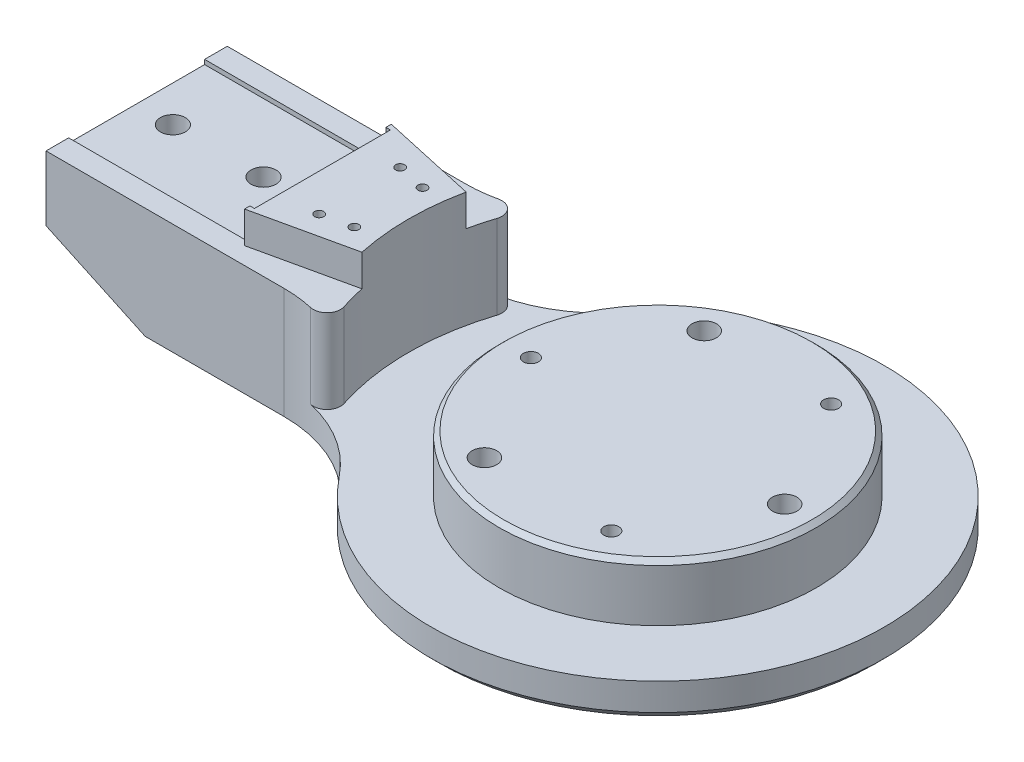
SolidWorks part; units mm, degrees
ref_plane "Front Plane" through (0, 0, 0) normal (0, 0, 1) x (1, 0, 0)
ref_plane "Top Plane" through (0, 0, 0) normal (0, 1, 0) x (1, 0, 0)
ref_plane "Right Plane" through (0, 0, 0) normal (1, 0, 0) x (0, 0, -1)
sketch "Sketch1" plane through (0, 0, 0) normal (0, 1, 0) x (1, 0, 0)
  circle A0 centre (0, 0) radius 35
  dimension "D1" = 70
extrude "Boss-Extrude1" add sketch "Sketch1" along normal blind 1
sketch "Sketch3" plane through (0, 0, 0) normal (0, -1, 0) x (1, 0, 0)
  line L1 (-28.2, -28.2) -> (28.2, -28.2) construction
  line L2 (-28.2, -28.2) -> (-28.2, 28.2) construction
  line L3 (-28.2, 28.2) -> (28.2, 28.2) construction
  line L4 (28.2, -28.2) -> (28.2, 28.2) construction
  line L5 (-28.2, -28.2) -> (28.2, 28.2) construction
  line L6 (-28.2, 28.2) -> (28.2, -28.2) construction
  circle A0 centre (0, 0) radius 50
  point P0 (0, 0)
  dimension "D2" = 100
  dimension "D1" = 56.4
extrude "Boss-Extrude3" add sketch "Sketch3" along normal blind 8
sketch "Sketch22" plane through (0, -8, 0) normal (0, -1, 0) x (1, 0, 0)
  line L0 (-50, 0) -> (-115, 0) construction
  line L1 (-45.8258, 20) -> (-115, 20)
  line L2 (-45.8258, -20) -> (-115, -20)
  line L4 (-115, 20) -> (-115, -20)
  line L5 (-1.6087, 20) -> (-95.5859, 20) construction
  line L6 (-1.6087, 0) -> (-95.5859, 0) construction
  line L7 (-1.6087, -20) -> (-95.5859, -20) construction
  circle A0 centre (0, 0) radius 50 construction
  arc A1 (-45.8258, 20) -> (-45.8258, -20) centre (0, 0) ccw
  dimension "D3" = 115
  dimension "D1" = 20
  dimension "D2" = 20
extrude "Boss-Extrude5" add sketch "Sketch22" against normal up to surface (8 mm away) up to face at (0, 0, 35)
sketch "Sketch24" plane through (0, 0, 0) normal (0, 1, 0) x (1, 0, 0)
  line L3 (-115, -20) -> (-51.2348, -20)
  line L4 (-115, 20) -> (-115, -20)
  line L5 (-51.2348, 20) -> (-115, 20)
  line L6 (0, 0) -> (-127.3918, 0) construction
  arc A0 (-51.2348, 20) -> (-51.2348, -20) centre (0, 0) ccw
  dimension "D1" = 110
  dimension "D2" = 40
  dimension "D3" = 115
extrude "Boss-Extrude6" add sketch "Sketch24" along normal blind 18.5
fillet "Fillet1" radius 30 2 edges at (-45.8258, -4, -20) (-45.8258, -4, 20)
sketch "Sketch25" plane through (-115, 0, 0) normal (-1, 0, 0) x (0, 0, 1)
  line L0 (-20, 18.5) -> (20, 18.5) construction
  line L1 (-15, 19.5) -> (15, 19.5)
  line L2 (-15, 19.5) -> (-15, 17.5)
  line L3 (-15, 17.5) -> (15, 17.5)
  line L4 (15, 19.5) -> (15, 17.5)
  line L5 (-15, 19.5) -> (15, 17.5) construction
  line L6 (-15, 17.5) -> (15, 19.5) construction
  point P0 (0, 18.5)
  dimension "D1" = 2
  dimension "D2" = 30
extrude "Cut-Extrude14" cut sketch "Sketch25" against normal blind 41
sketch "Sketch26" plane through (0, -8, 0) normal (0, -1, 0) x (1, 0, 0)
  line L0 (-110.0843, 0) -> (-45.9178, 0) construction
  line L3 (-115, 20) -> (-115, -20) construction
  circle A0 centre (-107, 0) radius 2.75
  circle A1 centre (-87, 0) radius 2.75
  dimension "D3" = 5.5
  dimension "D1" = 8
  dimension "D2" = 20
extrude "Cut-Extrude15" cut sketch "Sketch26" against normal through all
sketch "Sketch27" plane through (0, -8, 0) normal (0, -1, 0) x (1, 0, 0)
  line L1 (-82.2805, -0.3743) -> (-84.3161, 3.9)
  line L2 (-84.3161, 3.9) -> (-89.0356, 4.2743)
  line L3 (-89.0356, 4.2743) -> (-91.7195, 0.3743)
  line L4 (-91.7195, 0.3743) -> (-89.6839, -3.9)
  line L5 (-89.6839, -3.9) -> (-84.9644, -4.2743)
  line L6 (-84.9644, -4.2743) -> (-82.2805, -0.3743)
  line L7 (-102.2805, -0.3743) -> (-104.3161, 3.9)
  line L8 (-104.3161, 3.9) -> (-109.0356, 4.2743)
  line L9 (-109.0356, 4.2743) -> (-111.7195, 0.3743)
  line L10 (-111.7195, 0.3743) -> (-109.6839, -3.9)
  line L11 (-109.6839, -3.9) -> (-104.9644, -4.2743)
  line L12 (-104.9644, -4.2743) -> (-102.2805, -0.3743)
  circle A0 centre (-87, 0) radius 4.1 construction
  circle A1 centre (-107, 0) radius 4.1 construction
  dimension "D1" = 8.2
extrude "Cut-Extrude16" cut sketch "Sketch27" against normal blind 12
sketch "Sketch30" plane through (0, -8, 0) normal (0, -1, 0) x (1, 0, 0)
  line L0 (0, 0) -> (143.771, 0) construction
sketch "Sketch31" plane through (0, 18.5, 0) normal (0, 1, 0) x (1, 0, 0)
  line L0 (-55, 0) -> (-75, 0) construction
  line L2 (-53.7849, -11.4971) -> (-75, -16.2003)
  line L8 (-115, -15) -> (-115, -20)
  line L9 (-115, -20) -> (-62.45, -20)
  line L10 (-62.45, 20) -> (-115, 20)
  line L15 (-115, -15) -> (-115, -20)
  line L23 (-75, -16.2003) -> (-75, 16.2003)
  line L24 (-53.7849, 11.4971) -> (-75, 16.2003)
  line L25 (-74, -15) -> (-115, -15)
  line L26 (-115, 20) -> (-115, 15)
  line L27 (-115, 15) -> (-74, 15)
  line L28 (-74, 15) -> (-74, -15)
  arc A3 (-50.119, -22.6514) -> (-62.45, -20) centre (-62.45, -50) ccw
  arc A4 (-50.119, 22.6514) -> (-50.119, -22.6514) centre (0, 0) ccw
  arc A5 (-50.119, -22.6514) -> (-62.45, -20) centre (-62.45, -50) ccw
  arc A7 (-53.7849, 11.4971) -> (-53.7849, -11.4971) centre (0, 0) ccw
  arc A9 (-62.45, 20) -> (-50.119, 22.6514) centre (-62.45, 50) ccw
  arc A10 (-62.45, 20) -> (-50.119, 22.6514) centre (-62.45, 50) ccw
  point P13 (-52.3713, 0)
  point P25 (-69, 0)
  arc M18 (-50.119, -22.6514) -> (-50.119, 22.6514) centre (0, 0) cw
  dimension "D2" = 20
  dimension "D3" = 25
  dimension "D1" = 0
extrude "Boss-Extrude7" add sketch "Sketch31" along normal blind 13 contours L0 A7 L24 L23 | L0 L23 L2 M18 region at (-64.835, 18.5, 0)
sketch "Sketch33" plane through (0, 31.5, 0) normal (0, 1, 0) x (1, 0, 0)
  line L0 (-55.0152, -11.7698) -> (-67.9999, -14.6485)
  line L1 (-53.7849, -11.4971) -> (-75, -16.2003) construction
  line L2 (-53.7849, -11.4971) -> (-75, -16.2003) construction
  line L3 (-67.9999, -14.6485) -> (-70.1065, -5.1463)
  line L5 (-57.0191, -2.7309) -> (-55.0152, -11.7698)
  line L6 (-48.9387, 0) -> (-52.4764, 0) construction
  line L8 (-57.0191, 2.7309) -> (-55.0152, 11.7698)
  line L9 (-55.0152, 11.7698) -> (-67.9999, 14.6485)
  line L10 (-67.9999, 14.6485) -> (-70.1065, 5.1463)
  line L12 (-57.0191, -2.7309) -> (-57.0191, 2.7309)
  line L13 (-70.1065, -5.1463) -> (-75, -5.1463)
  line L14 (-75, -16.2003) -> (-75, -15) construction
  line L15 (-70.1065, 5.1463) -> (-75, 5.1463)
  line L16 (-75, -5.1463) -> (-75, 5.1463)
  line L17 (-53.7849, 11.4971) -> (-75, 16.2003) construction
  point P6 (-57.0191, 2.7309)
  dimension "D1" = 13.3
extrude "Cut-Extrude21" cut sketch "Sketch33" against normal blind 6 contours L10 L15 L16 L13 L3 L0 L5 L12 L8 L9
sketch "Sketch34" plane through (0, 25.5, 0) normal (0, 1, 0) x (1, 0, 0)
  line L0 (-61.5075, 13.2091) -> (-63.5857, 3.835) construction
  line L1 (-55.0152, 11.7698) -> (-67.9999, 14.6485) construction
  line L2 (-57.0191, 0) -> (-74, 0) construction
  line L3 (-57.0191, -2.7309) -> (-57.0191, 2.7309) construction
  line L4 (-74, 15) -> (-74, -15) construction
  line L5 (-69.4068, 8.3025) -> (-56.422, 5.4239) construction
  line L6 (-67.9999, 14.6485) -> (-70.1065, 5.1463) construction
  line L7 (-57.0191, 2.7309) -> (-55.0152, 11.7698) construction
  line L8 (-67.9999, 14.6485) -> (-70.1065, 5.1463) construction
  line L9 (-69.1038, 9.6693) -> (-56.119, 6.7907) construction
  line L10 (-66.0874, 7.5666) -> (-64.5658, 14.4302) construction
  circle A0 centre (-59.4384, -7.5266) radius 1
  circle A1 centre (-65.7843, -8.9335) radius 1
  circle A2 centre (-65.7843, 8.9335) radius 1
  circle A4 centre (-59.4384, 7.5266) radius 1
  point P30 (-59.5633, 7.5666)
  point P31 (0, 0)
  point P32 (-65.7426, 8.9242)
  point P33 (0, 0)
  point P34 (-59.5845, 7.559)
  point P35 (0, 0)
  point P36 (0, 0)
  dimension "D1" = 6.5
  dimension "D3" = 3.25
  dimension "D2" = 1.4
extrude "Cut-Extrude22" cut sketch "Sketch34" against normal blind 5
chamfer "Chamfer4" distance 1 angle 45 1 edges at (0, 1, 35)
fillet "Fillet3" radius 3 2 edges at (-50.119, 9.25, -22.6514) (-50.119, 9.25, 22.6514)
chamfer "Chamfer6" distance 10 angle 65 1 edges at (-115, -8, 0) first distance on face at (-115, 11.625, 0)
chamfer "Chamfer7" distance 2 angle 45 7 edges at (-104.2775, -3, 20) (-78.0025, -8, 20) (-49.4596, -8, 22.9584) (50, -8, 0) (-49.4596, -8, -22.9584) (-78.0025, -8, -20) (-104.2775, -3, -20)
sketch "Sketch37" plane through (0, 25.5, 0) normal (0, 1, 0) x (1, 0, 0)
  line L1 (-61.4174, -14.5064) -> (-48.5826, -14.5064)
  line L2 (-61.4174, -14.5064) -> (-61.4174, 14.5064)
  line L3 (-61.4174, 14.5064) -> (-48.5826, 14.5064)
  line L4 (-48.5826, -14.5064) -> (-48.5826, 14.5064)
  line L5 (-61.4174, -14.5064) -> (-48.5826, 14.5064) construction
  line L6 (-61.4174, 14.5064) -> (-48.5826, -14.5064) construction
  arc A0 (-52.3439, 16.8854) -> (-52.3439, -16.8854) centre (0, 0) ccw construction
  point P0 (-55, 0)
extrude "Cut-Extrude24" cut sketch "Sketch37" along normal blind 15
sketch "Sketch38" plane through (0, 25.5, 0) normal (0, 1, 0) x (1, 0, 0)
  circle A0 centre (-75.6748, -4.6987) radius 27.8917
extrude "Cut-Extrude25" cut sketch "Sketch38" along normal up to surface (6 mm away) up to face at (-72.6844, 31.5, 11.8569)
sketch "Sketch39" plane through (0, 0, 0) normal (0, 1, 0) x (1, 0, 0)
  circle A0 centre (0, 0) radius 35
extrude "Boss-Extrude8" add sketch "Sketch39" along normal blind 12.5
chamfer "Chamfer8" distance 1 angle 45 1 edges at (0, 12.5, 35)
sketch "Sketch40" plane through (0, 12.5, 0) normal (0, 1, 0) x (1, 0, 0)
  line L0 (0, 0) -> (-20.2203, 35.0225) construction
  line L1 (0, 0) -> (-8.2923, 0) construction
  circle A0 centre (0, 0) radius 28 construction
  circle A1 centre (-14, 24.2487) radius 2.7
  point P5 (-14, 24.2487)
  dimension "D1" = 56
  dimension "D2" = 5.4
  dimension "D3" = 60
extrude "Cut-Extrude26" cut sketch "Sketch40" against normal blind 6.5 contours A1
pattern_circular "CirPattern1" count 3 over 360 about axis through (0, 12.5, 0) along (0, 1, 0) of "Cut-Extrude26"
sketch "Sketch41" plane through (0, 12.5, 0) normal (0, 1, 0) x (1, 0, 0)
  line L0 (-21.0636, 0) -> (0, 0) construction
  line L1 (0, 0) -> (-58.1465, 0) construction
  circle A0 centre (-28, 0) radius 1.65
  dimension "D3" = 3.3
  dimension "D1" = 0
  dimension "D2" = 28
extrude "Cut-Extrude27" cut sketch "Sketch41" against normal through all
sketch "Sketch42" plane through (0, -8, 0) normal (0, -1, 0) x (1, 0, 0)
  circle A0 centre (-28, 0) radius 3
  dimension "D1" = 6
extrude "Cut-Extrude28" cut sketch "Sketch42" against normal blind 14
pattern_circular "CirPattern2" count 3 over 360 about axis through (0, 12.5, 0) along (0, 1, 0) of "Cut-Extrude27", "Cut-Extrude28"
chamfer "Chamfer9" distance 1 angle 45 3 edges at (14, 6, 22.5987) (-28, 6, -1.65) (14, 6, -25.8987)
